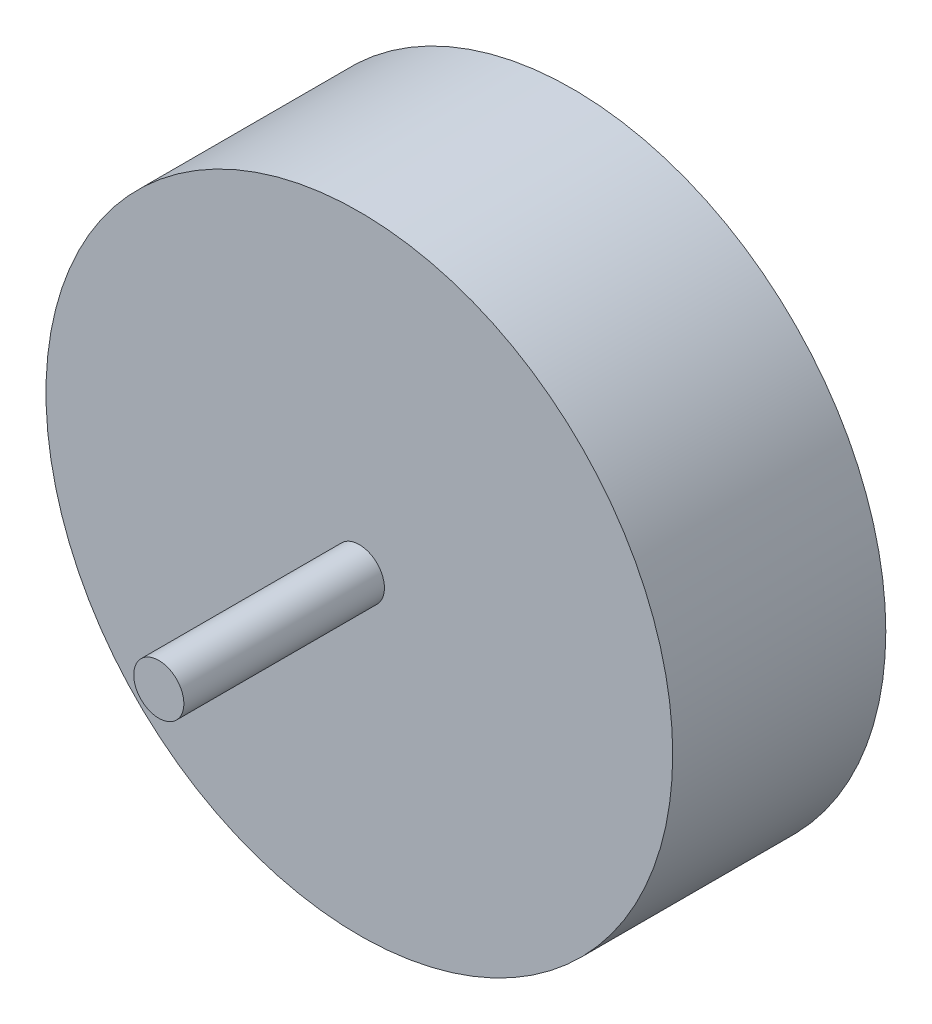
SolidWorks part; units mm, degrees
ref_plane "Front Plane" through (0, 0, 0) normal (0, 0, 1) x (1, 0, 0)
ref_plane "Top Plane" through (0, 0, 0) normal (0, 1, 0) x (1, 0, 0)
ref_plane "Right Plane" through (0, 0, 0) normal (1, 0, 0) x (0, 0, -1)
sketch "Sketch1" plane through (0, 0, 0) normal (0, 0, 1) x (1, 0, 0)
  circle A0 centre (0, 0) radius 25
  dimension "D1" = 50
extrude "Boss-Extrude1" add sketch "Sketch1" along normal blind 17
sketch "Sketch2" plane through (0, 0, 17) normal (0, 0, 1) x (1, 0, 0)
  circle A0 centre (0, 0) radius 2
  dimension "D1" = 4
extrude "Boss-Extrude2" add sketch "Sketch2" along normal blind 16
